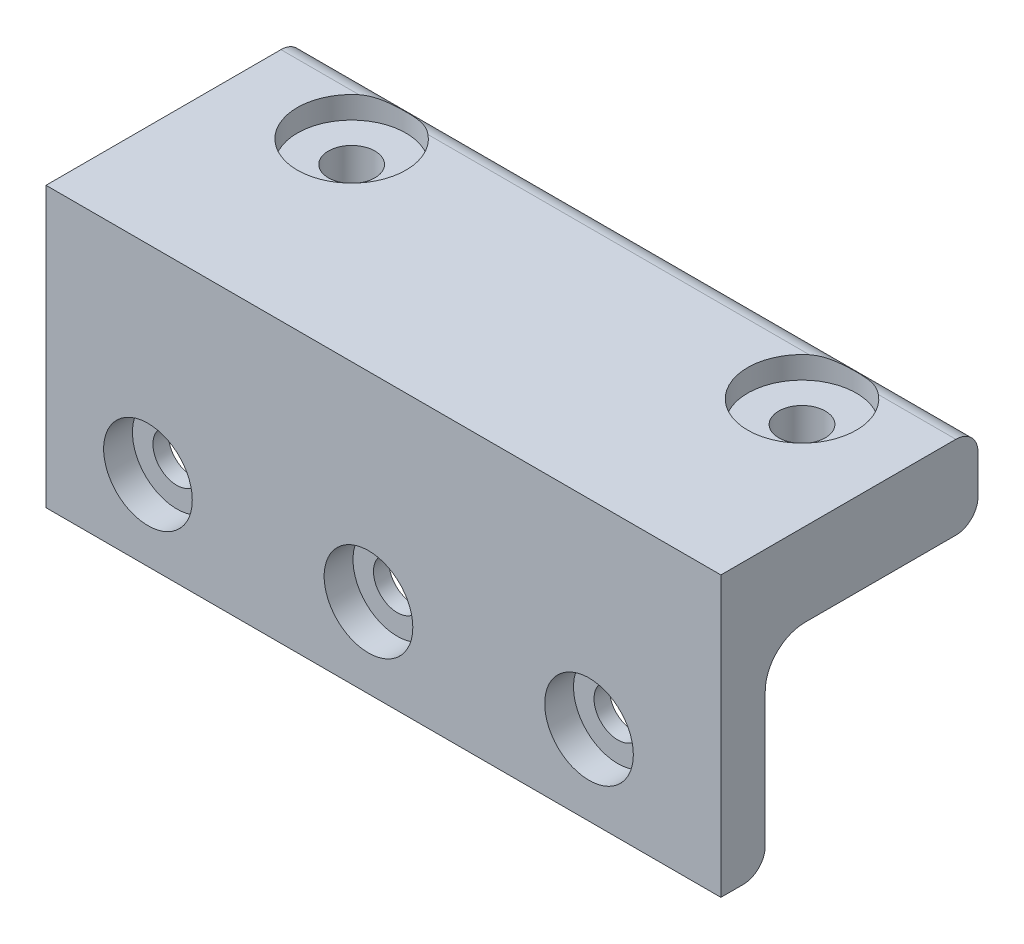
SolidWorks part; units mm, degrees
ref_plane "Front Plane" through (0, 0, 0) normal (0, 0, 1) x (1, 0, 0)
ref_plane "Top Plane" through (0, 0, 0) normal (0, 1, 0) x (1, 0, 0)
ref_plane "Right Plane" through (0, 0, 0) normal (1, 0, 0) x (0, 0, -1)
sketch "Sketch1" plane through (0, 0, 0) normal (0, 0, 1) x (1, 0, 0)
  line L1 (0, 0) -> (60.9, 0)
  line L2 (0, 0) -> (0, -25.2)
  line L3 (0, -25.2) -> (60.9, -25.2)
  line L4 (60.9, 0) -> (60.9, -25.2)
  dimension "D1" = 25.2
  dimension "D2" = 60.9
extrude "Boss-Extrude1" add sketch "Sketch1" against normal blind 4
sketch "Sketch3" plane through (0, 0, 0) normal (0, 0, 1) x (1, 0, 0)
  line L0 (0, 0) -> (0, -25.2) construction
  line L1 (60.9, 0) -> (0, 0) construction
  circle A0 centre (9.2, -18) radius 4
  circle A1 centre (29.1, -18) radius 4
  circle A2 centre (49, -18) radius 4
  circle A3 centre (9.2, -18) radius 2.15
  circle A4 centre (29.1, -18) radius 2.15
  circle A5 centre (49, -18) radius 2.15
  dimension "D1" = 8
  dimension "D2" = 8
  dimension "D3" = 8
  dimension "D8" = 4.3
  dimension "D9" = 4.3
  dimension "D10" = 4.3
  dimension "D4" = 9.2
  dimension "D5" = 29.1
  dimension "D6" = 49
  dimension "D7" = 18
extrude "Cut-Extrude1" cut sketch "Sketch3" against normal blind 2.6
extrude "Cut-Extrude2" cut sketch "Sketch3<2>" against normal through all contours A3 | A4 | A5 region at (9.2, -18, 0) region at (29.1, -18, 0) region at (49, -18, 0)
sketch "Sketch3<2>" plane through (0, 0, 0) normal (0, 0, 1) x (1, 0, 0) same geometry as "Sketch3"
sketch "Sketch4" plane through (0, 0, 0) normal (-1, 0, 0) x (0, 0, 1)
  line L0 (-4, -7.5) -> (-23.2, -7.5)
  line L1 (-4, 0) -> (-4, -25.2) construction
  line L2 (-23.2, -7.5) -> (-23.2, 0)
  line L3 (-23.2, 0) -> (-4, 0)
  line L4 (0, 0) -> (0, -25.2) construction
  line L5 (-4, 0) -> (-4, -7.5)
  dimension "D1" = 7.5
  dimension "D2" = 23.2
extrude "Boss-Extrude2" add sketch "Sketch4" against normal up to surface (60.9 mm away) up to face at (60.9, -12.6, -2)
sketch "Sketch5" plane through (0, 0, 0) normal (0, 1, 0) x (1, 0, 0)
  line L0 (60.9, 0) -> (0, 0) construction
  line L1 (0, 23.2) -> (0, 0) construction
  circle A0 centre (10.16, 17.42) radius 4.9
  circle A1 centre (50.8, 17.42) radius 4.9
  dimension "D1" = 9.8
  dimension "D2" = 9.8
  dimension "D3" = 40.64
  dimension "D4" = 17.42
  dimension "D5" = 10.16
extrude "Cut-Extrude3" cut sketch "Sketch5" against normal blind 2
hole_wizard "M5x0.8 Tapped Hole1" positions "Sketch6" profile "Sketch7" tap size "M5x0.8" standard "ANSI Metric" end condition through all
sketch "Sketch6" plane through (0, -2, 0) normal (0, 1, 0) x (1, 0, 0)
  point P0 (10.16, 17.42)
  point P3 (50.8, 17.42)
sketch "Sketch7" plane through (10.16, -2, -17.42) normal (1, 0, 0) x (0, 0, 1)
  line L0 (0, 0) -> (0, 23.2)
  line L1 (0, 23.2) -> (2.1, 23.2)
  line L2 (2.1, 23.2) -> (2.1, 0)
  line L5 (2.1, 0) -> (0, 0)
  line L11 (0, -6.35) -> (0, 107.95) construction
  dimension "Thru Tap Drill Dia." = 4.2
  dimension "Thru Tap Drill Depth" = 23.2
cosmetic thread "Hole Thread1" parameters "D2"=5
cosmetic thread "Hole Thread2" parameters "D2"=5
fillet "Fillet1" radius 2 3 edges at (30.45, 0, -23.2) (30.45, -25.2, -4) (30.45, -7.5, -23.2)
fillet "Fillet2" radius 3.6 1 edges at (30.45, -7.5, -4)
